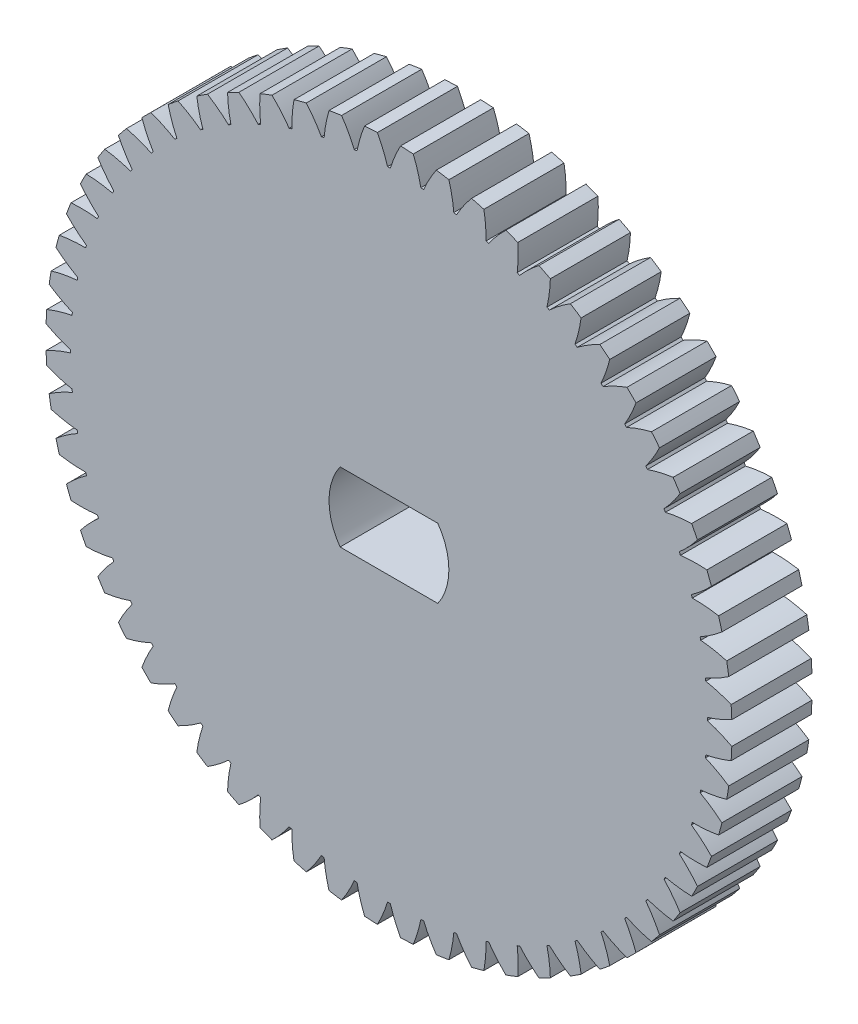
SolidWorks part; units mm, degrees
ref_plane "Front Plane" through (0, 0, 0) normal (0, 0, 1) x (1, 0, 0)
ref_plane "Top Plane" through (0, 0, 0) normal (0, 1, 0) x (1, 0, 0)
ref_plane "Right Plane" through (0, 0, 0) normal (1, 0, 0) x (0, 0, -1)
sketch "Sketch2" plane through (0, 0, 0) normal (0, 0, 1) x (1, 0, 0)
  line L0 (2, 1.5) -> (-2, 1.5)
  line L1 (-2, -1.5) -> (2, -1.5)
  line L2 (1.9365, 1.375) -> (-1.9365, 1.375)
  line L3 (-1.9365, -1.375) -> (1.9365, -1.375)
  circle A0 centre (0, 0) radius 0.4329 construction
  arc A1 (-13.4081, 0.5627) -> (-12.4437, 0.1861) centre (-11.0456, 5.1892) ccw
  arc A2 (-12.4437, 0.1861) -> (-12.4437, -0.1861) centre (0, 0) ccw
  arc A3 (-12.4437, -0.1861) -> (-13.4081, -0.5627) centre (-11.0456, -5.1892) ccw
  arc A4 (-13.4081, -0.5627) -> (-13.3935, -0.8419) centre (0, 0) ccw
  arc A5 (-13.3935, -0.8419) -> (-12.3949, -1.1156) centre (-11.5275, 4.0062) ccw
  arc A6 (-12.3949, -1.1156) -> (-12.356, -1.4858) centre (0, 0) ccw
  arc A7 (-12.356, -1.4858) -> (-13.2759, -1.9612) centre (-10.4427, -6.3154) ccw
  arc A8 (-13.2759, -1.9612) -> (-13.2321, -2.2373) centre (0, 0) ccw
  arc A9 (-13.2321, -2.2373) -> (-12.2104, -2.4052) centre (-11.8831, 2.7793) ccw
  arc A10 (-12.2104, -2.4052) -> (-12.1331, -2.7692) centre (0, 0) ccw
  arc A11 (-12.1331, -2.7692) -> (-12.9981, -3.3382) centre (-9.7253, -7.3724) ccw
  arc A12 (-12.9981, -3.3382) -> (-12.9258, -3.6081) centre (0, 0) ccw
  arc A13 (-12.9258, -3.6081) -> (-11.8921, -3.6683) centre (-12.1086, 1.522) ccw
  arc A14 (-11.8921, -3.6683) -> (-11.7771, -4.0223) centre (0, 0) ccw
  arc A15 (-11.7771, -4.0223) -> (-12.578, -4.6785) centre (-8.9014, -8.3485) ccw
  arc A16 (-12.578, -4.6785) -> (-12.4778, -4.9395) centre (0, 0) ccw
  arc A17 (-12.4778, -4.9395) -> (-11.4435, -4.8913) centre (-12.2013, 0.248) ccw
  arc A18 (-11.4435, -4.8913) -> (-11.2922, -5.2313) centre (0, 0) ccw
  arc A19 (-11.2922, -5.2313) -> (-12.0201, -5.9677) centre (-7.98, -9.2333) ccw
  arc A20 (-12.0201, -5.9677) -> (-11.8932, -6.2167) centre (0, 0) ccw
  arc A21 (-11.8932, -6.2167) -> (-10.8696, -6.0607) centre (-12.1604, -1.0288) ccw
  arc A22 (-10.8696, -6.0607) -> (-10.6835, -6.383) centre (0, 0) ccw
  arc A23 (-10.6835, -6.383) -> (-11.3304, -7.1914) centre (-6.9711, -10.0168) ccw
  arc A24 (-11.3304, -7.1914) -> (-11.1782, -7.4258) centre (0, 0) ccw
  arc A25 (-11.1782, -7.4258) -> (-10.1765, -7.1637) centre (-11.9862, -2.2943) ccw
  arc A26 (-10.1765, -7.1637) -> (-9.9578, -7.4648) centre (0, 0) ccw
  arc A27 (-9.9578, -7.4648) -> (-10.5166, -8.3364) centre (-5.8859, -10.6906) ccw
  arc A28 (-10.5166, -8.3364) -> (-10.3407, -8.5536) centre (0, 0) ccw
  arc A29 (-10.3407, -8.5536) -> (-9.372, -8.1881) centre (-11.6808, -3.5346) ccw
  arc A30 (-9.372, -8.1881) -> (-9.1229, -8.4647) centre (0, 0) ccw
  arc A31 (-9.1229, -8.4647) -> (-9.5876, -9.39) centre (-4.7362, -11.2473) ccw
  arc A32 (-9.5876, -9.39) -> (-9.39, -9.5876) centre (0, 0) ccw
  arc A33 (-9.39, -9.5876) -> (-8.4647, -9.1229) centre (-11.2473, -4.7362) ccw
  arc A34 (-8.4647, -9.1229) -> (-8.1881, -9.372) centre (0, 0) ccw
  arc A35 (-8.1881, -9.372) -> (-8.5536, -10.3407) centre (-3.5346, -11.6808) ccw
  arc A36 (-8.5536, -10.3407) -> (-8.3364, -10.5166) centre (0, 0) ccw
  arc A37 (-8.3364, -10.5166) -> (-7.4648, -9.9578) centre (-10.6906, -5.8859) ccw
  arc A38 (-7.4648, -9.9578) -> (-7.1637, -10.1765) centre (0, 0) ccw
  arc A39 (-7.1637, -10.1765) -> (-7.4258, -11.1782) centre (-2.2943, -11.9862) ccw
  arc A40 (-7.4258, -11.1782) -> (-7.1914, -11.3304) centre (0, 0) ccw
  arc A41 (-7.1914, -11.3304) -> (-6.383, -10.6835) centre (-10.0168, -6.9711) ccw
  arc A42 (-6.383, -10.6835) -> (-6.0607, -10.8696) centre (0, 0) ccw
  arc A43 (-6.0607, -10.8696) -> (-6.2167, -11.8932) centre (-1.0288, -12.1604) ccw
  arc A44 (-6.2167, -11.8932) -> (-5.9677, -12.0201) centre (0, 0) ccw
  arc A45 (-5.9677, -12.0201) -> (-5.2313, -11.2922) centre (-9.2333, -7.98) ccw
  arc A46 (-5.2313, -11.2922) -> (-4.8913, -11.4435) centre (0, 0) ccw
  arc A47 (-4.8913, -11.4435) -> (-4.9395, -12.4778) centre (0.248, -12.2013) ccw
  arc A48 (-4.9395, -12.4778) -> (-4.6785, -12.578) centre (0, 0) ccw
  arc A49 (-4.6785, -12.578) -> (-4.0223, -11.7771) centre (-8.3485, -8.9014) ccw
  arc A50 (-4.0223, -11.7771) -> (-3.6683, -11.8921) centre (0, 0) ccw
  arc A51 (-3.6683, -11.8921) -> (-3.6081, -12.9258) centre (1.522, -12.1086) ccw
  arc A52 (-3.6081, -12.9258) -> (-3.3382, -12.9981) centre (0, 0) ccw
  arc A53 (-3.3382, -12.9981) -> (-2.7692, -12.1331) centre (-7.3724, -9.7253) ccw
  arc A54 (-2.7692, -12.1331) -> (-2.4052, -12.2104) centre (0, 0) ccw
  arc A55 (-2.4052, -12.2104) -> (-2.2373, -13.2321) centre (2.7793, -11.8831) ccw
  arc A56 (-2.2373, -13.2321) -> (-1.9612, -13.2759) centre (0, 0) ccw
  arc A57 (-1.9612, -13.2759) -> (-1.4858, -12.356) centre (-6.3154, -10.4427) ccw
  arc A58 (-1.4858, -12.356) -> (-1.1156, -12.3949) centre (0, 0) ccw
  arc A59 (-1.1156, -12.3949) -> (-0.8419, -13.3935) centre (4.0062, -11.5275) ccw
  arc A60 (-0.8419, -13.3935) -> (-0.5627, -13.4081) centre (0, 0) ccw
  arc A61 (-0.5627, -13.4081) -> (-0.1861, -12.4437) centre (-5.1892, -11.0456) ccw
  arc A62 (-0.1861, -12.4437) -> (0.1861, -12.4437) centre (0, 0) ccw
  arc A63 (0.1861, -12.4437) -> (0.5627, -13.4081) centre (5.1892, -11.0456) ccw
  arc A64 (0.5627, -13.4081) -> (0.8419, -13.3935) centre (0, 0) ccw
  arc A65 (0.8419, -13.3935) -> (1.1156, -12.3949) centre (-4.0062, -11.5275) ccw
  arc A66 (1.1156, -12.3949) -> (1.4858, -12.356) centre (0, 0) ccw
  arc A67 (1.4858, -12.356) -> (1.9612, -13.2759) centre (6.3154, -10.4427) ccw
  arc A68 (1.9612, -13.2759) -> (2.2373, -13.2321) centre (0, 0) ccw
  arc A69 (2.2373, -13.2321) -> (2.4052, -12.2104) centre (-2.7793, -11.8831) ccw
  arc A70 (2.4052, -12.2104) -> (2.7692, -12.1331) centre (0, 0) ccw
  arc A71 (2.7692, -12.1331) -> (3.3382, -12.9981) centre (7.3724, -9.7253) ccw
  arc A72 (3.3382, -12.9981) -> (3.6081, -12.9258) centre (0, 0) ccw
  arc A73 (3.6081, -12.9258) -> (3.6683, -11.8921) centre (-1.522, -12.1086) ccw
  arc A74 (3.6683, -11.8921) -> (4.0223, -11.7771) centre (0, 0) ccw
  arc A75 (4.0223, -11.7771) -> (4.6785, -12.578) centre (8.3485, -8.9014) ccw
  arc A76 (4.6785, -12.578) -> (4.9395, -12.4778) centre (0, 0) ccw
  arc A77 (4.9395, -12.4778) -> (4.8913, -11.4435) centre (-0.248, -12.2013) ccw
  arc A78 (4.8913, -11.4435) -> (5.2313, -11.2922) centre (0, 0) ccw
  arc A79 (5.2313, -11.2922) -> (5.9677, -12.0201) centre (9.2333, -7.98) ccw
  arc A80 (5.9677, -12.0201) -> (6.2167, -11.8932) centre (0, 0) ccw
  arc A81 (6.2167, -11.8932) -> (6.0607, -10.8696) centre (1.0288, -12.1604) ccw
  arc A82 (6.0607, -10.8696) -> (6.383, -10.6835) centre (0, 0) ccw
  arc A83 (6.383, -10.6835) -> (7.1914, -11.3304) centre (10.0168, -6.9711) ccw
  arc A84 (7.1914, -11.3304) -> (7.4258, -11.1782) centre (0, 0) ccw
  arc A85 (7.4258, -11.1782) -> (7.1637, -10.1765) centre (2.2943, -11.9862) ccw
  arc A86 (7.1637, -10.1765) -> (7.4648, -9.9578) centre (0, 0) ccw
  arc A87 (7.4648, -9.9578) -> (8.3364, -10.5166) centre (10.6906, -5.8859) ccw
  arc A88 (8.3364, -10.5166) -> (8.5536, -10.3407) centre (0, 0) ccw
  arc A89 (8.5536, -10.3407) -> (8.1881, -9.372) centre (3.5346, -11.6808) ccw
  arc A90 (8.1881, -9.372) -> (8.4647, -9.1229) centre (0, 0) ccw
  arc A91 (8.4647, -9.1229) -> (9.39, -9.5876) centre (11.2473, -4.7362) ccw
  arc A92 (9.39, -9.5876) -> (9.5876, -9.39) centre (0, 0) ccw
  arc A93 (9.5876, -9.39) -> (9.1229, -8.4647) centre (4.7362, -11.2473) ccw
  arc A94 (9.1229, -8.4647) -> (9.372, -8.1881) centre (0, 0) ccw
  arc A95 (9.372, -8.1881) -> (10.3407, -8.5536) centre (11.6808, -3.5346) ccw
  arc A96 (10.3407, -8.5536) -> (10.5166, -8.3364) centre (0, 0) ccw
  arc A97 (10.5166, -8.3364) -> (9.9578, -7.4648) centre (5.8859, -10.6906) ccw
  arc A98 (9.9578, -7.4648) -> (10.1765, -7.1637) centre (0, 0) ccw
  arc A99 (10.1765, -7.1637) -> (11.1782, -7.4258) centre (11.9862, -2.2943) ccw
  arc A100 (11.1782, -7.4258) -> (11.3304, -7.1914) centre (0, 0) ccw
  arc A101 (11.3304, -7.1914) -> (10.6835, -6.383) centre (6.9711, -10.0168) ccw
  arc A102 (10.6835, -6.383) -> (10.8696, -6.0607) centre (0, 0) ccw
  arc A103 (10.8696, -6.0607) -> (11.8932, -6.2167) centre (12.1604, -1.0288) ccw
  arc A104 (11.8932, -6.2167) -> (12.0201, -5.9677) centre (0, 0) ccw
  arc A105 (12.0201, -5.9677) -> (11.2922, -5.2313) centre (7.98, -9.2333) ccw
  arc A106 (11.2922, -5.2313) -> (11.4435, -4.8913) centre (0, 0) ccw
  arc A107 (11.4435, -4.8913) -> (12.4778, -4.9395) centre (12.2013, 0.248) ccw
  arc A108 (12.4778, -4.9395) -> (12.578, -4.6785) centre (0, 0) ccw
  arc A109 (12.578, -4.6785) -> (11.7771, -4.0223) centre (8.9014, -8.3485) ccw
  arc A110 (11.7771, -4.0223) -> (11.8921, -3.6683) centre (0, 0) ccw
  arc A111 (11.8921, -3.6683) -> (12.9258, -3.6081) centre (12.1086, 1.522) ccw
  arc A112 (12.9258, -3.6081) -> (12.9981, -3.3382) centre (0, 0) ccw
  arc A113 (12.9981, -3.3382) -> (12.1331, -2.7692) centre (9.7253, -7.3724) ccw
  arc A114 (12.1331, -2.7692) -> (12.2104, -2.4052) centre (0, 0) ccw
  arc A115 (12.2104, -2.4052) -> (13.2321, -2.2373) centre (11.8831, 2.7793) ccw
  arc A116 (13.2321, -2.2373) -> (13.2759, -1.9612) centre (0, 0) ccw
  arc A117 (13.2759, -1.9612) -> (12.356, -1.4858) centre (10.4427, -6.3154) ccw
  arc A118 (12.356, -1.4858) -> (12.3949, -1.1156) centre (0, 0) ccw
  arc A119 (12.3949, -1.1156) -> (13.3935, -0.8419) centre (11.5275, 4.0062) ccw
  arc A120 (13.3935, -0.8419) -> (13.4081, -0.5627) centre (0, 0) ccw
  arc A121 (13.4081, -0.5627) -> (12.4437, -0.1861) centre (11.0456, -5.1892) ccw
  arc A122 (12.4437, -0.1861) -> (12.4437, 0.1861) centre (0, 0) ccw
  arc A123 (12.4437, 0.1861) -> (13.4081, 0.5627) centre (11.0456, 5.1892) ccw
  arc A124 (13.4081, 0.5627) -> (13.3935, 0.8419) centre (0, 0) ccw
  arc A125 (13.3935, 0.8419) -> (12.3949, 1.1156) centre (11.5275, -4.0062) ccw
  arc A126 (12.3949, 1.1156) -> (12.356, 1.4858) centre (0, 0) ccw
  arc A127 (12.356, 1.4858) -> (13.2759, 1.9612) centre (10.4427, 6.3154) ccw
  arc A128 (13.2759, 1.9612) -> (13.2321, 2.2373) centre (0, 0) ccw
  arc A129 (13.2321, 2.2373) -> (12.2104, 2.4052) centre (11.8831, -2.7793) ccw
  arc A130 (12.2104, 2.4052) -> (12.1331, 2.7692) centre (0, 0) ccw
  arc A131 (12.1331, 2.7692) -> (12.9981, 3.3382) centre (9.7253, 7.3724) ccw
  arc A132 (12.9981, 3.3382) -> (12.9258, 3.6081) centre (0, 0) ccw
  arc A133 (12.9258, 3.6081) -> (11.8921, 3.6683) centre (12.1086, -1.522) ccw
  arc A134 (11.8921, 3.6683) -> (11.7771, 4.0223) centre (0, 0) ccw
  arc A135 (11.7771, 4.0223) -> (12.578, 4.6785) centre (8.9014, 8.3485) ccw
  arc A136 (12.578, 4.6785) -> (12.4778, 4.9395) centre (0, 0) ccw
  arc A137 (12.4778, 4.9395) -> (11.4435, 4.8913) centre (12.2013, -0.248) ccw
  arc A138 (11.4435, 4.8913) -> (11.2922, 5.2313) centre (0, 0) ccw
  arc A139 (11.2922, 5.2313) -> (12.0201, 5.9677) centre (7.98, 9.2333) ccw
  arc A140 (12.0201, 5.9677) -> (11.8932, 6.2167) centre (0, 0) ccw
  arc A141 (11.8932, 6.2167) -> (10.8696, 6.0607) centre (12.1604, 1.0288) ccw
  arc A142 (10.8696, 6.0607) -> (10.6835, 6.383) centre (0, 0) ccw
  arc A143 (10.6835, 6.383) -> (11.3304, 7.1914) centre (6.9711, 10.0168) ccw
  arc A144 (11.3304, 7.1914) -> (11.1782, 7.4258) centre (0, 0) ccw
  arc A145 (11.1782, 7.4258) -> (10.1765, 7.1637) centre (11.9862, 2.2943) ccw
  arc A146 (10.1765, 7.1637) -> (9.9578, 7.4648) centre (0, 0) ccw
  arc A147 (9.9578, 7.4648) -> (10.5166, 8.3364) centre (5.8859, 10.6906) ccw
  arc A148 (10.5166, 8.3364) -> (10.3407, 8.5536) centre (0, 0) ccw
  arc A149 (10.3407, 8.5536) -> (9.372, 8.1881) centre (11.6808, 3.5346) ccw
  arc A150 (9.372, 8.1881) -> (9.1229, 8.4647) centre (0, 0) ccw
  arc A151 (9.1229, 8.4647) -> (9.5876, 9.39) centre (4.7362, 11.2473) ccw
  arc A152 (9.5876, 9.39) -> (9.39, 9.5876) centre (0, 0) ccw
  arc A153 (9.39, 9.5876) -> (8.4647, 9.1229) centre (11.2473, 4.7362) ccw
  arc A154 (8.4647, 9.1229) -> (8.1881, 9.372) centre (0, 0) ccw
  arc A155 (8.1881, 9.372) -> (8.5536, 10.3407) centre (3.5346, 11.6808) ccw
  arc A156 (8.5536, 10.3407) -> (8.3364, 10.5166) centre (0, 0) ccw
  arc A157 (8.3364, 10.5166) -> (7.4648, 9.9578) centre (10.6906, 5.8859) ccw
  arc A158 (7.4648, 9.9578) -> (7.1637, 10.1765) centre (0, 0) ccw
  arc A159 (7.1637, 10.1765) -> (7.4258, 11.1782) centre (2.2943, 11.9862) ccw
  arc A160 (7.4258, 11.1782) -> (7.1914, 11.3304) centre (0, 0) ccw
  arc A161 (7.1914, 11.3304) -> (6.383, 10.6835) centre (10.0168, 6.9711) ccw
  arc A162 (6.383, 10.6835) -> (6.0607, 10.8696) centre (0, 0) ccw
  arc A163 (6.0607, 10.8696) -> (6.2167, 11.8932) centre (1.0288, 12.1604) ccw
  arc A164 (6.2167, 11.8932) -> (5.9677, 12.0201) centre (0, 0) ccw
  arc A165 (5.9677, 12.0201) -> (5.2313, 11.2922) centre (9.2333, 7.98) ccw
  arc A166 (5.2313, 11.2922) -> (4.8913, 11.4435) centre (0, 0) ccw
  arc A167 (4.8913, 11.4435) -> (4.9395, 12.4778) centre (-0.248, 12.2013) ccw
  arc A168 (4.9395, 12.4778) -> (4.6785, 12.578) centre (0, 0) ccw
  arc A169 (4.6785, 12.578) -> (4.0223, 11.7771) centre (8.3485, 8.9014) ccw
  arc A170 (4.0223, 11.7771) -> (3.6683, 11.8921) centre (0, 0) ccw
  arc A171 (3.6683, 11.8921) -> (3.6081, 12.9258) centre (-1.522, 12.1086) ccw
  arc A172 (3.6081, 12.9258) -> (3.3382, 12.9981) centre (0, 0) ccw
  arc A173 (3.3382, 12.9981) -> (2.7692, 12.1331) centre (7.3724, 9.7253) ccw
  arc A174 (2.7692, 12.1331) -> (2.4052, 12.2104) centre (0, 0) ccw
  arc A175 (2.4052, 12.2104) -> (2.2373, 13.2321) centre (-2.7793, 11.8831) ccw
  arc A176 (2.2373, 13.2321) -> (1.9612, 13.2759) centre (0, 0) ccw
  arc A177 (1.9612, 13.2759) -> (1.4858, 12.356) centre (6.3154, 10.4427) ccw
  arc A178 (1.4858, 12.356) -> (1.1156, 12.3949) centre (0, 0) ccw
  arc A179 (1.1156, 12.3949) -> (0.8419, 13.3935) centre (-4.0062, 11.5275) ccw
  arc A180 (0.8419, 13.3935) -> (0.5627, 13.4081) centre (0, 0) ccw
  arc A181 (0.5627, 13.4081) -> (0.1861, 12.4437) centre (5.1892, 11.0456) ccw
  arc A182 (0.1861, 12.4437) -> (-0.1861, 12.4437) centre (0, 0) ccw
  arc A183 (-0.1861, 12.4437) -> (-0.5627, 13.4081) centre (-5.1892, 11.0456) ccw
  arc A184 (-0.5627, 13.4081) -> (-0.8419, 13.3935) centre (0, 0) ccw
  arc A185 (-0.8419, 13.3935) -> (-1.1156, 12.3949) centre (4.0062, 11.5275) ccw
  arc A186 (-1.1156, 12.3949) -> (-1.4858, 12.356) centre (0, 0) ccw
  arc A187 (-1.4858, 12.356) -> (-1.9612, 13.2759) centre (-6.3154, 10.4427) ccw
  arc A188 (-1.9612, 13.2759) -> (-2.2373, 13.2321) centre (0, 0) ccw
  arc A189 (-2.2373, 13.2321) -> (-2.4052, 12.2104) centre (2.7793, 11.8831) ccw
  arc A190 (-2.4052, 12.2104) -> (-2.7692, 12.1331) centre (0, 0) ccw
  arc A191 (-2.7692, 12.1331) -> (-3.3382, 12.9981) centre (-7.3724, 9.7253) ccw
  arc A192 (-3.3382, 12.9981) -> (-3.6081, 12.9258) centre (0, 0) ccw
  arc A193 (-3.6081, 12.9258) -> (-3.6683, 11.8921) centre (1.522, 12.1086) ccw
  arc A194 (-3.6683, 11.8921) -> (-4.0223, 11.7771) centre (0, 0) ccw
  arc A195 (-4.0223, 11.7771) -> (-4.6785, 12.578) centre (-8.3485, 8.9014) ccw
  arc A196 (-4.6785, 12.578) -> (-4.9395, 12.4778) centre (0, 0) ccw
  arc A197 (-4.9395, 12.4778) -> (-4.8913, 11.4435) centre (0.248, 12.2013) ccw
  arc A198 (-4.8913, 11.4435) -> (-5.2313, 11.2922) centre (0, 0) ccw
  arc A199 (-5.2313, 11.2922) -> (-5.9677, 12.0201) centre (-9.2333, 7.98) ccw
  arc A200 (-5.9677, 12.0201) -> (-6.2167, 11.8932) centre (0, 0) ccw
  arc A201 (-6.2167, 11.8932) -> (-6.0607, 10.8696) centre (-1.0288, 12.1604) ccw
  arc A202 (-6.0607, 10.8696) -> (-6.383, 10.6835) centre (0, 0) ccw
  arc A203 (-6.383, 10.6835) -> (-7.1914, 11.3304) centre (-10.0168, 6.9711) ccw
  arc A204 (-7.1914, 11.3304) -> (-7.4258, 11.1782) centre (0, 0) ccw
  arc A205 (-7.4258, 11.1782) -> (-7.1637, 10.1765) centre (-2.2943, 11.9862) ccw
  arc A206 (-7.1637, 10.1765) -> (-7.4648, 9.9578) centre (0, 0) ccw
  arc A207 (-7.4648, 9.9578) -> (-8.3364, 10.5166) centre (-10.6906, 5.8859) ccw
  arc A208 (-8.3364, 10.5166) -> (-8.5536, 10.3407) centre (0, 0) ccw
  arc A209 (-8.5536, 10.3407) -> (-8.1881, 9.372) centre (-3.5346, 11.6808) ccw
  arc A210 (-8.1881, 9.372) -> (-8.4647, 9.1229) centre (0, 0) ccw
  arc A211 (-8.4647, 9.1229) -> (-9.39, 9.5876) centre (-11.2473, 4.7362) ccw
  arc A212 (-9.39, 9.5876) -> (-9.5876, 9.39) centre (0, 0) ccw
  arc A213 (-9.5876, 9.39) -> (-9.1229, 8.4647) centre (-4.7362, 11.2473) ccw
  arc A214 (-9.1229, 8.4647) -> (-9.372, 8.1881) centre (0, 0) ccw
  arc A215 (-9.372, 8.1881) -> (-10.3407, 8.5536) centre (-11.6808, 3.5346) ccw
  arc A216 (-10.3407, 8.5536) -> (-10.5166, 8.3364) centre (0, 0) ccw
  arc A217 (-10.5166, 8.3364) -> (-9.9578, 7.4648) centre (-5.8859, 10.6906) ccw
  arc A218 (-9.9578, 7.4648) -> (-10.1765, 7.1637) centre (0, 0) ccw
  arc A219 (-10.1765, 7.1637) -> (-11.1782, 7.4258) centre (-11.9862, 2.2943) ccw
  arc A220 (-11.1782, 7.4258) -> (-11.3304, 7.1914) centre (0, 0) ccw
  arc A221 (-11.3304, 7.1914) -> (-10.6835, 6.383) centre (-6.9711, 10.0168) ccw
  arc A222 (-10.6835, 6.383) -> (-10.8696, 6.0607) centre (0, 0) ccw
  arc A223 (-10.8696, 6.0607) -> (-11.8932, 6.2167) centre (-12.1604, 1.0288) ccw
  arc A224 (-11.8932, 6.2167) -> (-12.0201, 5.9677) centre (0, 0) ccw
  arc A225 (-12.0201, 5.9677) -> (-11.2922, 5.2313) centre (-7.98, 9.2333) ccw
  arc A226 (-11.2922, 5.2313) -> (-11.4435, 4.8913) centre (0, 0) ccw
  arc A227 (-11.4435, 4.8913) -> (-12.4778, 4.9395) centre (-12.2013, -0.248) ccw
  arc A228 (-12.4778, 4.9395) -> (-12.578, 4.6785) centre (0, 0) ccw
  arc A229 (-12.578, 4.6785) -> (-11.7771, 4.0223) centre (-8.9014, 8.3485) ccw
  arc A230 (-11.7771, 4.0223) -> (-11.8921, 3.6683) centre (0, 0) ccw
  arc A231 (-11.8921, 3.6683) -> (-12.9258, 3.6081) centre (-12.1086, -1.522) ccw
  arc A232 (-12.9258, 3.6081) -> (-12.9981, 3.3382) centre (0, 0) ccw
  arc A233 (-12.9981, 3.3382) -> (-12.1331, 2.7692) centre (-9.7253, 7.3724) ccw
  arc A234 (-12.1331, 2.7692) -> (-12.2104, 2.4052) centre (0, 0) ccw
  arc A235 (-12.2104, 2.4052) -> (-13.2321, 2.2373) centre (-11.8831, -2.7793) ccw
  arc A236 (-13.2321, 2.2373) -> (-13.2759, 1.9612) centre (0, 0) ccw
  arc A237 (-13.2759, 1.9612) -> (-12.356, 1.4858) centre (-10.4427, 6.3154) ccw
  arc A238 (-12.356, 1.4858) -> (-12.3949, 1.1156) centre (0, 0) ccw
  arc A239 (-12.3949, 1.1156) -> (-13.3935, 0.8419) centre (-11.5275, -4.0062) ccw
  arc A240 (-13.3935, 0.8419) -> (-13.4081, 0.5627) centre (0, 0) ccw
  arc A241 (-2, 1.5) -> (-2, -1.5) centre (0, 0) ccw
  arc A242 (2, -1.5) -> (2, 1.5) centre (0, 0) ccw
  arc A723 (9.3414, 8.4856) -> (9.7901, 9.4327) centre (4.7362, 11.2473) ccw
  arc A724 (9.7901, 9.4327) -> (9.4327, 9.7901) centre (0, 0) ccw
  arc A725 (9.4327, 9.7901) -> (8.4856, 9.3414) centre (11.2473, 4.7362) ccw
  arc A726 (8.4856, 9.3414) -> (8.4032, 9.4155) centre (0, 0) ccw
  arc A727 (8.4032, 9.4155) -> (8.7505, 10.4044) centre (3.5346, 11.6808) ccw
  arc A728 (8.7505, 10.4044) -> (8.3577, 10.7225) centre (0, 0) ccw
  arc A729 (8.3577, 10.7225) -> (7.4626, 10.1772) centre (10.6906, 5.8859) ccw
  arc A730 (7.4626, 10.1772) -> (7.373, 10.2423) centre (0, 0) ccw
  arc A731 (7.373, 10.2423) -> (7.615, 11.2621) centre (2.2943, 11.9862) ccw
  arc A732 (7.615, 11.2621) -> (7.1911, 11.5374) centre (0, 0) ccw
  arc A733 (7.1911, 11.5374) -> (6.3579, 10.9015) centre (10.0168, 6.9711) ccw
  arc A734 (6.3579, 10.9015) -> (6.262, 10.9569) centre (0, 0) ccw
  arc A735 (6.262, 10.9569) -> (6.3961, 11.9964) centre (1.0288, 12.1604) ccw
  arc A736 (6.3961, 11.9964) -> (5.9457, 12.2258) centre (0, 0) ccw
  arc A737 (5.9457, 12.2258) -> (5.1836, 11.5064) centre (9.2333, 7.98) ccw
  arc A738 (5.1836, 11.5064) -> (5.0824, 11.5514) centre (0, 0) ccw
  arc A739 (5.0824, 11.5514) -> (5.1071, 12.5992) centre (-0.248, 12.2013) ccw
  arc A740 (5.1071, 12.5992) -> (4.6352, 12.7804) centre (0, 0) ccw
  arc A741 (4.6352, 12.7804) -> (3.9525, 11.9852) centre (8.3485, 8.9014) ccw
  arc A742 (3.9525, 11.9852) -> (3.8471, 12.0194) centre (0, 0) ccw
  arc A743 (3.8471, 12.0194) -> (3.7621, 13.064) centre (-1.522, 12.1086) ccw
  arc A744 (3.7621, 13.064) -> (3.2739, 13.1949) centre (0, 0) ccw
  arc A745 (3.2739, 13.1949) -> (2.678, 12.3326) centre (7.3724, 9.7253) ccw
  arc A746 (2.678, 12.3326) -> (2.5696, 12.3557) centre (0, 0) ccw
  arc A747 (2.5696, 12.3557) -> (2.376, 13.3857) centre (-2.7793, 11.8831) ccw
  arc A748 (2.376, 13.3857) -> (1.8767, 13.4648) centre (0, 0) ccw
  arc A749 (1.8767, 13.4648) -> (1.3742, 12.545) centre (6.3154, 10.4427) ccw
  arc A750 (1.3742, 12.545) -> (1.264, 12.5566) centre (0, 0) ccw
  arc A751 (1.264, 12.5566) -> (0.9638, 13.5607) centre (-4.0062, 11.5275) ccw
  arc A752 (0.9638, 13.5607) -> (0.459, 13.5872) centre (0, 0) ccw
  arc A753 (0.459, 13.5872) -> (0.0554, 12.6199) centre (5.1892, 11.0456) ccw
  arc A754 (0.0554, 12.6199) -> (-0.0554, 12.6199) centre (0, 0) ccw
  arc A755 (-0.0554, 12.6199) -> (-0.459, 13.5872) centre (-5.1892, 11.0456) ccw
  arc A756 (-0.459, 13.5872) -> (-0.9638, 13.5607) centre (0, 0) ccw
  arc A757 (-0.9638, 13.5607) -> (-1.264, 12.5566) centre (4.0062, 11.5275) ccw
  arc A758 (-1.264, 12.5566) -> (-1.3742, 12.545) centre (0, 0) ccw
  arc A759 (-1.3742, 12.545) -> (-1.8767, 13.4648) centre (-6.3154, 10.4427) ccw
  arc A760 (-1.8767, 13.4648) -> (-2.376, 13.3857) centre (0, 0) ccw
  arc A761 (-2.376, 13.3857) -> (-2.5696, 12.3557) centre (2.7793, 11.8831) ccw
  arc A762 (-2.5696, 12.3557) -> (-2.678, 12.3326) centre (0, 0) ccw
  arc A763 (-2.678, 12.3326) -> (-3.2739, 13.1949) centre (-7.3724, 9.7253) ccw
  arc A764 (-3.2739, 13.1949) -> (-3.7621, 13.064) centre (0, 0) ccw
  arc A765 (-3.7621, 13.064) -> (-3.8471, 12.0194) centre (1.522, 12.1086) ccw
  arc A766 (-3.8471, 12.0194) -> (-3.9525, 11.9852) centre (0, 0) ccw
  arc A767 (-3.9525, 11.9852) -> (-4.6352, 12.7804) centre (-8.3485, 8.9014) ccw
  arc A768 (-4.6352, 12.7804) -> (-5.1071, 12.5992) centre (0, 0) ccw
  arc A769 (-5.1071, 12.5992) -> (-5.0824, 11.5514) centre (0.248, 12.2013) ccw
  arc A770 (-5.0824, 11.5514) -> (-5.1836, 11.5064) centre (0, 0) ccw
  arc A771 (-5.1836, 11.5064) -> (-5.9457, 12.2258) centre (-9.2333, 7.98) ccw
  arc A772 (-5.9457, 12.2258) -> (-6.3961, 11.9964) centre (0, 0) ccw
  arc A773 (-6.3961, 11.9964) -> (-6.262, 10.9569) centre (-1.0288, 12.1604) ccw
  arc A774 (-6.262, 10.9569) -> (-6.3579, 10.9015) centre (0, 0) ccw
  arc A775 (-6.3579, 10.9015) -> (-7.1911, 11.5374) centre (-10.0168, 6.9711) ccw
  arc A776 (-7.1911, 11.5374) -> (-7.615, 11.2621) centre (0, 0) ccw
  arc A777 (-7.615, 11.2621) -> (-7.373, 10.2423) centre (-2.2943, 11.9862) ccw
  arc A778 (-7.373, 10.2423) -> (-7.4626, 10.1772) centre (0, 0) ccw
  arc A779 (-7.4626, 10.1772) -> (-8.3577, 10.7225) centre (-10.6906, 5.8859) ccw
  arc A780 (-8.3577, 10.7225) -> (-8.7505, 10.4044) centre (0, 0) ccw
  arc A781 (-8.7505, 10.4044) -> (-8.4032, 9.4155) centre (-3.5346, 11.6808) ccw
  arc A782 (-8.4032, 9.4155) -> (-8.4856, 9.3414) centre (0, 0) ccw
  arc A783 (-8.4856, 9.3414) -> (-9.4327, 9.7901) centre (-11.2473, 4.7362) ccw
  arc A784 (-9.4327, 9.7901) -> (-9.7901, 9.4327) centre (0, 0) ccw
  arc A785 (-9.7901, 9.4327) -> (-9.3414, 8.4856) centre (-4.7362, 11.2473) ccw
  arc A786 (-9.3414, 8.4856) -> (-9.4155, 8.4032) centre (0, 0) ccw
  arc A787 (-9.4155, 8.4032) -> (-10.4044, 8.7505) centre (-11.6808, 3.5346) ccw
  arc A788 (-10.4044, 8.7505) -> (-10.7225, 8.3577) centre (0, 0) ccw
  arc A789 (-10.7225, 8.3577) -> (-10.1772, 7.4626) centre (-5.8859, 10.6906) ccw
  arc A790 (-10.1772, 7.4626) -> (-10.2423, 7.373) centre (0, 0) ccw
  arc A791 (-10.2423, 7.373) -> (-11.2621, 7.615) centre (-11.9862, 2.2943) ccw
  arc A792 (-11.2621, 7.615) -> (-11.5374, 7.1911) centre (0, 0) ccw
  arc A793 (-11.5374, 7.1911) -> (-10.9015, 6.3579) centre (-6.9711, 10.0168) ccw
  arc A794 (-10.9015, 6.3579) -> (-10.9569, 6.262) centre (0, 0) ccw
  arc A795 (-10.9569, 6.262) -> (-11.9964, 6.3961) centre (-12.1604, 1.0288) ccw
  arc A796 (-11.9964, 6.3961) -> (-12.2258, 5.9457) centre (0, 0) ccw
  arc A797 (-12.2258, 5.9457) -> (-11.5064, 5.1836) centre (-7.98, 9.2333) ccw
  arc A798 (-11.5064, 5.1836) -> (-11.5514, 5.0824) centre (0, 0) ccw
  arc A799 (-11.5514, 5.0824) -> (-12.5992, 5.1071) centre (-12.2013, -0.248) ccw
  arc A800 (-12.5992, 5.1071) -> (-12.7804, 4.6352) centre (0, 0) ccw
  arc A801 (-12.7804, 4.6352) -> (-11.9852, 3.9525) centre (-8.9014, 8.3485) ccw
  arc A802 (-11.9852, 3.9525) -> (-12.0194, 3.8471) centre (0, 0) ccw
  arc A803 (-12.0194, 3.8471) -> (-13.064, 3.7621) centre (-12.1086, -1.522) ccw
  arc A804 (-13.064, 3.7621) -> (-13.1949, 3.2739) centre (0, 0) ccw
  arc A805 (-13.1949, 3.2739) -> (-12.3326, 2.678) centre (-9.7253, 7.3724) ccw
  arc A806 (-12.3326, 2.678) -> (-12.3557, 2.5696) centre (0, 0) ccw
  arc A807 (-12.3557, 2.5696) -> (-13.3857, 2.376) centre (-11.8831, -2.7793) ccw
  arc A808 (-13.3857, 2.376) -> (-13.4648, 1.8767) centre (0, 0) ccw
  arc A809 (-13.4648, 1.8767) -> (-12.545, 1.3742) centre (-10.4427, 6.3154) ccw
  arc A810 (-12.545, 1.3742) -> (-12.5566, 1.264) centre (0, 0) ccw
  arc A811 (-12.5566, 1.264) -> (-13.5607, 0.9638) centre (-11.5275, -4.0062) ccw
  arc A812 (-13.5607, 0.9638) -> (-13.5872, 0.459) centre (0, 0) ccw
  arc A813 (-13.5872, 0.459) -> (-12.6199, 0.0554) centre (-11.0456, 5.1892) ccw
  arc A814 (-12.6199, 0.0554) -> (-12.6199, -0.0554) centre (0, 0) ccw
  arc A815 (-12.6199, -0.0554) -> (-13.5872, -0.459) centre (-11.0456, -5.1892) ccw
  arc A816 (-13.5872, -0.459) -> (-13.5607, -0.9638) centre (0, 0) ccw
  arc A817 (-13.5607, -0.9638) -> (-12.5566, -1.264) centre (-11.5275, 4.0062) ccw
  arc A818 (-12.5566, -1.264) -> (-12.545, -1.3742) centre (0, 0) ccw
  arc A819 (-12.545, -1.3742) -> (-13.4648, -1.8767) centre (-10.4427, -6.3154) ccw
  arc A820 (-13.4648, -1.8767) -> (-13.3857, -2.376) centre (0, 0) ccw
  arc A821 (-13.3857, -2.376) -> (-12.3557, -2.5696) centre (-11.8831, 2.7793) ccw
  arc A822 (-12.3557, -2.5696) -> (-12.3326, -2.678) centre (0, 0) ccw
  arc A823 (-12.3326, -2.678) -> (-13.1949, -3.2739) centre (-9.7253, -7.3724) ccw
  arc A824 (-13.1949, -3.2739) -> (-13.064, -3.7621) centre (0, 0) ccw
  arc A825 (-13.064, -3.7621) -> (-12.0194, -3.8471) centre (-12.1086, 1.522) ccw
  arc A826 (-12.0194, -3.8471) -> (-11.9852, -3.9525) centre (0, 0) ccw
  arc A827 (-11.9852, -3.9525) -> (-12.7804, -4.6352) centre (-8.9014, -8.3485) ccw
  arc A828 (-12.7804, -4.6352) -> (-12.5992, -5.1071) centre (0, 0) ccw
  arc A829 (-12.5992, -5.1071) -> (-11.5514, -5.0824) centre (-12.2013, 0.248) ccw
  arc A830 (-11.5514, -5.0824) -> (-11.5064, -5.1836) centre (0, 0) ccw
  arc A831 (-11.5064, -5.1836) -> (-12.2258, -5.9457) centre (-7.98, -9.2333) ccw
  arc A832 (-12.2258, -5.9457) -> (-11.9964, -6.3961) centre (0, 0) ccw
  arc A833 (-11.9964, -6.3961) -> (-10.9569, -6.262) centre (-12.1604, -1.0288) ccw
  arc A834 (-10.9569, -6.262) -> (-10.9015, -6.3579) centre (0, 0) ccw
  arc A835 (-10.9015, -6.3579) -> (-11.5374, -7.1911) centre (-6.9711, -10.0168) ccw
  arc A836 (-11.5374, -7.1911) -> (-11.2621, -7.615) centre (0, 0) ccw
  arc A837 (-11.2621, -7.615) -> (-10.2423, -7.373) centre (-11.9862, -2.2943) ccw
  arc A838 (-10.2423, -7.373) -> (-10.1772, -7.4626) centre (0, 0) ccw
  arc A839 (-10.1772, -7.4626) -> (-10.7225, -8.3577) centre (-5.8859, -10.6906) ccw
  arc A840 (-10.7225, -8.3577) -> (-10.4044, -8.7505) centre (0, 0) ccw
  arc A841 (-10.4044, -8.7505) -> (-9.4155, -8.4032) centre (-11.6808, -3.5346) ccw
  arc A842 (-9.4155, -8.4032) -> (-9.3414, -8.4856) centre (0, 0) ccw
  arc A843 (-9.3414, -8.4856) -> (-9.7901, -9.4327) centre (-4.7362, -11.2473) ccw
  arc A844 (-9.7901, -9.4327) -> (-9.4327, -9.7901) centre (0, 0) ccw
  arc A845 (-9.4327, -9.7901) -> (-8.4856, -9.3414) centre (-11.2473, -4.7362) ccw
  arc A846 (-8.4856, -9.3414) -> (-8.4032, -9.4155) centre (0, 0) ccw
  arc A847 (-8.4032, -9.4155) -> (-8.7505, -10.4044) centre (-3.5346, -11.6808) ccw
  arc A848 (-8.7505, -10.4044) -> (-8.3577, -10.7225) centre (0, 0) ccw
  arc A849 (-8.3577, -10.7225) -> (-7.4626, -10.1772) centre (-10.6906, -5.8859) ccw
  arc A850 (-7.4626, -10.1772) -> (-7.373, -10.2423) centre (0, 0) ccw
  arc A851 (-7.373, -10.2423) -> (-7.615, -11.2621) centre (-2.2943, -11.9862) ccw
  arc A852 (-7.615, -11.2621) -> (-7.1911, -11.5374) centre (0, 0) ccw
  arc A853 (-7.1911, -11.5374) -> (-6.3579, -10.9015) centre (-10.0168, -6.9711) ccw
  arc A854 (-6.3579, -10.9015) -> (-6.262, -10.9569) centre (0, 0) ccw
  arc A855 (-6.262, -10.9569) -> (-6.3961, -11.9964) centre (-1.0288, -12.1604) ccw
  arc A856 (-6.3961, -11.9964) -> (-5.9457, -12.2258) centre (0, 0) ccw
  arc A857 (-5.9457, -12.2258) -> (-5.1836, -11.5064) centre (-9.2333, -7.98) ccw
  arc A858 (-5.1836, -11.5064) -> (-5.0824, -11.5514) centre (0, 0) ccw
  arc A859 (-5.0824, -11.5514) -> (-5.1071, -12.5992) centre (0.248, -12.2013) ccw
  arc A860 (-5.1071, -12.5992) -> (-4.6352, -12.7804) centre (0, 0) ccw
  arc A861 (-4.6352, -12.7804) -> (-3.9525, -11.9852) centre (-8.3485, -8.9014) ccw
  arc A862 (-3.9525, -11.9852) -> (-3.8471, -12.0194) centre (0, 0) ccw
  arc A863 (-3.8471, -12.0194) -> (-3.7621, -13.064) centre (1.522, -12.1086) ccw
  arc A864 (-3.7621, -13.064) -> (-3.2739, -13.1949) centre (0, 0) ccw
  arc A865 (-3.2739, -13.1949) -> (-2.678, -12.3326) centre (-7.3724, -9.7253) ccw
  arc A866 (-2.678, -12.3326) -> (-2.5696, -12.3557) centre (0, 0) ccw
  arc A867 (-2.5696, -12.3557) -> (-2.376, -13.3857) centre (2.7793, -11.8831) ccw
  arc A868 (-2.376, -13.3857) -> (-1.8767, -13.4648) centre (0, 0) ccw
  arc A869 (-1.8767, -13.4648) -> (-1.3742, -12.545) centre (-6.3154, -10.4427) ccw
  arc A870 (-1.3742, -12.545) -> (-1.264, -12.5566) centre (0, 0) ccw
  arc A871 (-1.264, -12.5566) -> (-0.9638, -13.5607) centre (4.0062, -11.5275) ccw
  arc A872 (-0.9638, -13.5607) -> (-0.459, -13.5872) centre (0, 0) ccw
  arc A873 (-0.459, -13.5872) -> (-0.0554, -12.6199) centre (-5.1892, -11.0456) ccw
  arc A874 (-0.0554, -12.6199) -> (0.0554, -12.6199) centre (0, 0) ccw
  arc A875 (0.0554, -12.6199) -> (0.459, -13.5872) centre (5.1892, -11.0456) ccw
  arc A876 (0.459, -13.5872) -> (0.9638, -13.5607) centre (0, 0) ccw
  arc A877 (0.9638, -13.5607) -> (1.264, -12.5566) centre (-4.0062, -11.5275) ccw
  arc A878 (1.264, -12.5566) -> (1.3742, -12.545) centre (0, 0) ccw
  arc A879 (1.3742, -12.545) -> (1.8767, -13.4648) centre (6.3154, -10.4427) ccw
  arc A880 (1.8767, -13.4648) -> (2.376, -13.3857) centre (0, 0) ccw
  arc A881 (2.376, -13.3857) -> (2.5696, -12.3557) centre (-2.7793, -11.8831) ccw
  arc A882 (2.5696, -12.3557) -> (2.678, -12.3326) centre (0, 0) ccw
  arc A883 (2.678, -12.3326) -> (3.2739, -13.1949) centre (7.3724, -9.7253) ccw
  arc A884 (3.2739, -13.1949) -> (3.7621, -13.064) centre (0, 0) ccw
  arc A885 (3.7621, -13.064) -> (3.8471, -12.0194) centre (-1.522, -12.1086) ccw
  arc A886 (3.8471, -12.0194) -> (3.9525, -11.9852) centre (0, 0) ccw
  arc A887 (3.9525, -11.9852) -> (4.6352, -12.7804) centre (8.3485, -8.9014) ccw
  arc A888 (4.6352, -12.7804) -> (5.1071, -12.5992) centre (0, 0) ccw
  arc A889 (5.1071, -12.5992) -> (5.0824, -11.5514) centre (-0.248, -12.2013) ccw
  arc A890 (5.0824, -11.5514) -> (5.1836, -11.5064) centre (0, 0) ccw
  arc A891 (5.1836, -11.5064) -> (5.9457, -12.2258) centre (9.2333, -7.98) ccw
  arc A892 (5.9457, -12.2258) -> (6.3961, -11.9964) centre (0, 0) ccw
  arc A893 (6.3961, -11.9964) -> (6.262, -10.9569) centre (1.0288, -12.1604) ccw
  arc A894 (6.262, -10.9569) -> (6.3579, -10.9015) centre (0, 0) ccw
  arc A895 (6.3579, -10.9015) -> (7.1911, -11.5374) centre (10.0168, -6.9711) ccw
  arc A896 (7.1911, -11.5374) -> (7.615, -11.2621) centre (0, 0) ccw
  arc A897 (7.615, -11.2621) -> (7.373, -10.2423) centre (2.2943, -11.9862) ccw
  arc A898 (7.373, -10.2423) -> (7.4626, -10.1772) centre (0, 0) ccw
  arc A899 (7.4626, -10.1772) -> (8.3577, -10.7225) centre (10.6906, -5.8859) ccw
  arc A900 (8.3577, -10.7225) -> (8.7505, -10.4044) centre (0, 0) ccw
  arc A901 (8.7505, -10.4044) -> (8.4032, -9.4155) centre (3.5346, -11.6808) ccw
  arc A902 (8.4032, -9.4155) -> (8.4856, -9.3414) centre (0, 0) ccw
  arc A903 (8.4856, -9.3414) -> (9.4327, -9.7901) centre (11.2473, -4.7362) ccw
  arc A904 (9.4327, -9.7901) -> (9.7901, -9.4327) centre (0, 0) ccw
  arc A905 (9.7901, -9.4327) -> (9.3414, -8.4856) centre (4.7362, -11.2473) ccw
  arc A906 (9.3414, -8.4856) -> (9.4155, -8.4032) centre (0, 0) ccw
  arc A907 (9.4155, -8.4032) -> (10.4044, -8.7505) centre (11.6808, -3.5346) ccw
  arc A908 (10.4044, -8.7505) -> (10.7225, -8.3577) centre (0, 0) ccw
  arc A909 (10.7225, -8.3577) -> (10.1772, -7.4626) centre (5.8859, -10.6906) ccw
  arc A910 (10.1772, -7.4626) -> (10.2423, -7.373) centre (0, 0) ccw
  arc A911 (10.2423, -7.373) -> (11.2621, -7.615) centre (11.9862, -2.2943) ccw
  arc A912 (11.2621, -7.615) -> (11.5374, -7.1911) centre (0, 0) ccw
  arc A913 (11.5374, -7.1911) -> (10.9015, -6.3579) centre (6.9711, -10.0168) ccw
  arc A914 (10.9015, -6.3579) -> (10.9569, -6.262) centre (0, 0) ccw
  arc A915 (10.9569, -6.262) -> (11.9964, -6.3961) centre (12.1604, -1.0288) ccw
  arc A916 (11.9964, -6.3961) -> (12.2258, -5.9457) centre (0, 0) ccw
  arc A917 (12.2258, -5.9457) -> (11.5064, -5.1836) centre (7.98, -9.2333) ccw
  arc A918 (11.5064, -5.1836) -> (11.5514, -5.0824) centre (0, 0) ccw
  arc A919 (11.5514, -5.0824) -> (12.5992, -5.1071) centre (12.2013, 0.248) ccw
  arc A920 (12.5992, -5.1071) -> (12.7804, -4.6352) centre (0, 0) ccw
  arc A921 (12.7804, -4.6352) -> (11.9852, -3.9525) centre (8.9014, -8.3485) ccw
  arc A922 (11.9852, -3.9525) -> (12.0194, -3.8471) centre (0, 0) ccw
  arc A923 (12.0194, -3.8471) -> (13.064, -3.7621) centre (12.1086, 1.522) ccw
  arc A924 (13.064, -3.7621) -> (13.1949, -3.2739) centre (0, 0) ccw
  arc A925 (13.1949, -3.2739) -> (12.3326, -2.678) centre (9.7253, -7.3724) ccw
  arc A926 (12.3326, -2.678) -> (12.3557, -2.5696) centre (0, 0) ccw
  arc A927 (12.3557, -2.5696) -> (13.3857, -2.376) centre (11.8831, 2.7793) ccw
  arc A928 (13.3857, -2.376) -> (13.4648, -1.8767) centre (0, 0) ccw
  arc A929 (13.4648, -1.8767) -> (12.545, -1.3742) centre (10.4427, -6.3154) ccw
  arc A930 (12.545, -1.3742) -> (12.5566, -1.264) centre (0, 0) ccw
  arc A931 (12.5566, -1.264) -> (13.5607, -0.9638) centre (11.5275, 4.0062) ccw
  arc A932 (13.5607, -0.9638) -> (13.5872, -0.459) centre (0, 0) ccw
  arc A933 (13.5872, -0.459) -> (12.6199, -0.0554) centre (11.0456, -5.1892) ccw
  arc A934 (12.6199, -0.0554) -> (12.6199, 0.0554) centre (0, 0) ccw
  arc A935 (12.6199, 0.0554) -> (13.5872, 0.459) centre (11.0456, 5.1892) ccw
  arc A936 (13.5872, 0.459) -> (13.5607, 0.9638) centre (0, 0) ccw
  arc A937 (13.5607, 0.9638) -> (12.5566, 1.264) centre (11.5275, -4.0062) ccw
  arc A938 (12.5566, 1.264) -> (12.545, 1.3742) centre (0, 0) ccw
  arc A939 (12.545, 1.3742) -> (13.4648, 1.8767) centre (10.4427, 6.3154) ccw
  arc A940 (13.4648, 1.8767) -> (13.3857, 2.376) centre (0, 0) ccw
  arc A941 (13.3857, 2.376) -> (12.3557, 2.5696) centre (11.8831, -2.7793) ccw
  arc A942 (12.3557, 2.5696) -> (12.3326, 2.678) centre (0, 0) ccw
  arc A943 (12.3326, 2.678) -> (13.1949, 3.2739) centre (9.7253, 7.3724) ccw
  arc A944 (13.1949, 3.2739) -> (13.064, 3.7621) centre (0, 0) ccw
  arc A945 (13.064, 3.7621) -> (12.0194, 3.8471) centre (12.1086, -1.522) ccw
  arc A946 (12.0194, 3.8471) -> (11.9852, 3.9525) centre (0, 0) ccw
  arc A947 (11.9852, 3.9525) -> (12.7804, 4.6352) centre (8.9014, 8.3485) ccw
  arc A948 (12.7804, 4.6352) -> (12.5992, 5.1071) centre (0, 0) ccw
  arc A949 (12.5992, 5.1071) -> (11.5514, 5.0824) centre (12.2013, -0.248) ccw
  arc A950 (11.5514, 5.0824) -> (11.5064, 5.1836) centre (0, 0) ccw
  arc A951 (11.5064, 5.1836) -> (12.2258, 5.9457) centre (7.98, 9.2333) ccw
  arc A952 (12.2258, 5.9457) -> (11.9964, 6.3961) centre (0, 0) ccw
  arc A953 (11.9964, 6.3961) -> (10.9569, 6.262) centre (12.1604, 1.0288) ccw
  arc A954 (10.9569, 6.262) -> (10.9015, 6.3579) centre (0, 0) ccw
  arc A955 (10.9015, 6.3579) -> (11.5374, 7.1911) centre (6.9711, 10.0168) ccw
  arc A956 (11.5374, 7.1911) -> (11.2621, 7.615) centre (0, 0) ccw
  arc A957 (11.2621, 7.615) -> (10.2423, 7.373) centre (11.9862, 2.2943) ccw
  arc A958 (10.2423, 7.373) -> (10.1772, 7.4626) centre (0, 0) ccw
  arc A959 (10.1772, 7.4626) -> (10.7225, 8.3577) centre (5.8859, 10.6906) ccw
  arc A960 (10.7225, 8.3577) -> (10.4044, 8.7505) centre (0, 0) ccw
  arc A961 (10.4044, 8.7505) -> (9.4155, 8.4032) centre (11.6808, 3.5346) ccw
  arc A962 (9.4155, 8.4032) -> (9.3414, 8.4856) centre (0, 0) ccw
  arc A963 (1.9365, -1.375) -> (1.9365, 1.375) centre (0, 0) ccw
  arc A964 (-1.9365, 1.375) -> (-1.9365, -1.375) centre (0, 0) ccw
  dimension "D1" = 5
  dimension "D2" = 3
  dimension "D3" = 1.5
  dimension "D4" = 0.125
  dimension "D6" = 0.175
extrude "Boss-Extrude1" add sketch "Sketch2" along normal blind 3.175 contours A239 A240 A1 A2 A3 A4 A5 A6 A7 A8 A9 A10 A11 A12 A13 A14 A15 A16 A17 A18 A19 A20 A21 A22 A23 A24 A25 A26 A27 A28 A29 A30 A31 A32 A33 A34 A35 A36 A37 A38 A39 A40 A41 A42 A43 A44 A45 A46 A47 A48 A49 | A961 A962 A723 A724 A725 A726 A727 A728 A729 A730 A731 A732 A733 A734 A735 A736 A737 A738 A739 A740 A741 A742 A743 A744 A745 A746 A747 A748 A749 A750 A751 A752 A753 A754 A755 A756 A757 A758 A759 A760 A761 A762 A763 A764 A765 A766 A767 A768 A769 A770 A771 | L1 A242 L0 A241 A964 L2 A963 L3 region at (2.4417, 0, 0) region at (-13.0228, 0.6825, 0) region at (9.35, 8.4188, 0)
